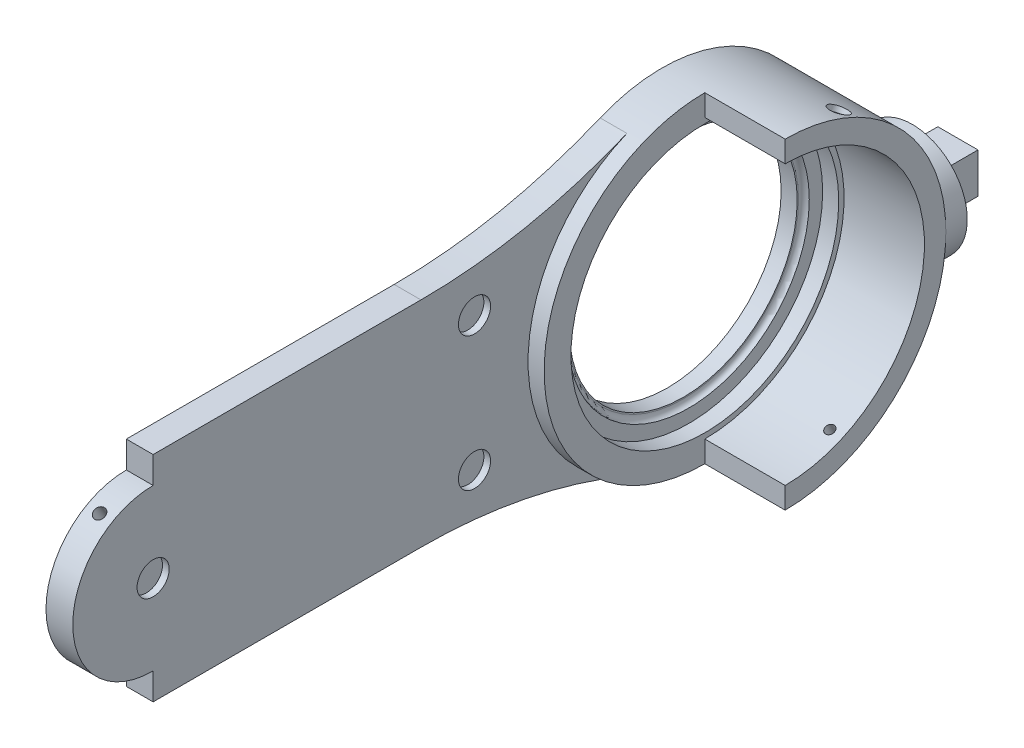
SolidWorks part; units mm, degrees
ref_plane "Front Plane" through (0, 0, 0) normal (0, 0, 1) x (1, 0, 0)
ref_plane "Top Plane" through (0, 0, 0) normal (0, 1, 0) x (1, 0, 0)
ref_plane "Right Plane" through (0, 0, 0) normal (1, 0, 0) x (0, 0, -1)
sketch "Sketch1" plane through (0, 0, 0) normal (1, 0, 0) x (0, 0, -1)
  line L0 (0, 0) -> (-200, 0) construction
  line L1 (-200, 40) -> (-200, -40) construction
  line L2 (-100, 40) -> (-100, -40) construction
  line L3 (-100, 40) -> (-200, 40)
  line L4 (-100, -40) -> (-200, -40)
  circle A0 centre (0, 0) radius 60
  circle A1 centre (0, 0) radius 45
  circle A2 centre (-200, 0) radius 40
  arc A3 (-100, 40) -> (-23.0769, 55.3846) centre (-100, 240) ccw
  arc A4 (-100, -40) -> (-23.0769, -55.3846) centre (-100, -240) cw
  circle A5 centre (-100, 0) radius 40 construction
  dimension "D1" = 120
  dimension "D2" = 90
  dimension "D4" = 80
  dimension "D3" = 200
extrude "Boss-Extrude3" add sketch "Sketch1" along normal blind 10 contours A0 A1 | A2 A0 | A2 region at (0, 0, 109.7273) region at (0, 0, 200) region at (0, 48.511, -32.3407)
sketch "Sketch4" plane through (10, 0, 0) normal (1, 0, 0) x (0, 0, -1)
  circle A0 centre (0, 0) radius 60
  circle A1 centre (0, 0) radius 50
  arc A2 (-23.0769, -55.3846) -> (-23.0769, 55.3846) centre (0, 0) ccw construction
  dimension "D1" = 100
extrude "Boss-Extrude4" add sketch "Sketch4" along normal blind 6
sketch "Sketch5" plane through (0, 0, 0) normal (-1, 0, 0) x (0, 0, 1)
  circle A0 centre (0, 0) radius 45 construction
  circle A1 centre (0, 0) radius 45
  circle A2 centre (0, 0) radius 42.5
  dimension "D1" = 85
extrude "Boss-Extrude5" add sketch "Sketch5" against normal offset from surface (8 mm away) 2 up to face at (10, 0, 120.2589)
fillet "Fillet1" radius 2 1 edges at (8, 0, -45)
sketch "Sketch6" plane through (0, 0, 0) normal (-1, 0, 0) x (0, 0, 1)
  circle A0 centre (0, 0) radius 42.5 construction
  circle A1 centre (0, 0) radius 42.5
  circle A2 centre (0, 0) radius 52.5
  dimension "D1" = 105
extrude "Cut-Extrude2" cut sketch "Sketch6" against normal blind 2
sketch "Sketch7" plane through (16, 0, 0) normal (1, 0, 0) x (0, 0, -1)
  line L0 (0, 60) -> (0, 50)
  line L1 (0, -50) -> (0, -60)
  circle A0 centre (0, 0) radius 60 construction
  circle A1 centre (0, 0) radius 50 construction
  circle A2 centre (0, 0) radius 50 construction
  arc A3 (0, -60) -> (0, 60) centre (0, 0) ccw
  arc A4 (0, -50) -> (0, 50) centre (0, 0) ccw
  arc A5 (0, -52) -> (0, 52) centre (0, 0) ccw
  circle M1 centre (0, 0) radius 60
  dimension "D1" = 2
extrude "Boss-Extrude6" add sketch "Sketch7" along normal blind 30 contours A5 L1 L0 M1 region at (16, 41.4777, -41.4777)
ref_plane "Plane2" through (0, 0, -60) normal (0, 0, -1) x (-1, 0, 0)
sketch "Sketch8" plane through (0, 0, -60) normal (0, 0, -1) x (-1, 0, 0)
  line L0 (-5, 0) -> (-46, 0) construction
  line L1 (-46, 60) -> (-46, -60) construction
  line L2 (-5, 0) -> (0, 0) construction
  circle A0 centre (-25.5, 0) radius 20.5
  point P10 (-46, 0)
  dimension "D1" = 41
  dimension "D2" = 5
extrude "Boss-Extrude7" add sketch "Sketch8" against normal up to surface up to face at (5, 0, 11.5385)
sketch "Sketch9" plane through (0, 0, -60) normal (0, 0, -1) x (-1, 0, 0)
  circle A0 centre (-25.5, 0) radius 15
  arc A1 (-5, 0) -> (-46, 0) centre (-25.5, 0) ccw construction
  arc A2 (-5, 0) -> (-46, 0) centre (-25.5, 0) ccw
  arc A4 (-46, 0) -> (-5, 0) centre (-25.5, 0) ccw
  dimension "D1" = 30
sketch "Sketch11" plane through (10, 0, 0) normal (1, 0, 0) x (0, 0, -1)
  line L0 (-200, 30) -> (-200, 40)
  line L1 (-200, -30) -> (-200, -40)
  arc A0 (-200, 40) -> (-200, -40) centre (-200, 0) ccw construction
  arc A1 (-200, 40) -> (-200, -40) centre (-200, 0) ccw
  arc A2 (-200, 30) -> (-200, -30) centre (-200, 0) ccw
  dimension "D1" = 10
extrude "Cut-Extrude4" cut sketch "Sketch11" against normal through all both and the other way through all
extrude "Boss-Extrude8" add sketch "Sketch9" along normal blind 8
sketch "Sketch12" plane through (0, 0, -60) normal (0, 0, -1) x (-1, 0, 0)
  line L1 (-33, -7.5) -> (-18, -7.5)
  line L2 (-33, -7.5) -> (-33, 7.5)
  line L3 (-33, 7.5) -> (-18, 7.5)
  line L4 (-18, -7.5) -> (-18, 7.5)
  line L5 (-33, -7.5) -> (-18, 7.5) construction
  line L6 (-33, 7.5) -> (-18, -7.5) construction
  point P0 (-25.5, 0)
  dimension "D1" = 15
extrude "Boss-Extrude9" add sketch "Sketch12" along normal blind 25
hole_wizard "CBORE for M3 Hexagon head bolts-Full thread-grades AB1" positions "3DSketch1" profile "Sketch13" counterbore size "M3" standard "GB" end condition up to next
sketch3d "3DSketch1"
  point P0 (41, -54.5436, -25)
  point P2 (41, 54.5436, -25)
  dimension "D1" = 5
  dimension "D2" = 25
  dimension "D3" = 5
  dimension "D4" = 25
sketch "Sketch13" plane through (41, -54.5436, -25) normal (1, 0, 0) x (0, 0.4167, -0.9091)
  line L0 (0, 0) -> (0, 8)
  line L1 (0, 8) -> (1.7, 8)
  line L3 (1.7, 8) -> (1.7, 2)
  line L4 (1.7, 2) -> (3.5, 2)
  line L5 (3.5, 2) -> (3.5, 0)
  line L7 (3.5, 0) -> (0, 0)
  line L11 (0, -6.35) -> (0, 107.95) construction
  dimension "Thru Hole Dia." = 3.4
  dimension "Thru Hole Depth" = 8
  dimension "C'Bore Dia." = 7
  dimension "C'Bore Depth" = 2
sketch3d "3DSketch2"
  circle A0 centre (5, 32.909, 219) radius 1.7 construction
  circle A1 centre (5, -32.909, 219) radius 1.7 construction
  circle A2 centre (5, 32.909, 219) radius 1.7
  circle A3 centre (5, -32.909, 219) radius 1.7
  point P0 (5.233, -19.8859, 222.4622)
  point P3 (5, 34.3812, 219.85)
  point P6 (5, -34.3812, 219.85)
  point P8 (5, 34.3812, 219.85)
  point P10 (5, -34.3812, 219.85)
ref_plane "Plane3" through (0, -119.5115, 69) normal (0, -0.866, 0.5) x (-1, 0, 0)
ref_plane "Plane4" through (0, 119.5115, 69) normal (0, 0.866, 0.5) x (1, 0, 0)
sketch "Sketch14" plane through (0, 119.5115, 69) normal (0, 0.866, 0.5) x (1, 0, 0)
  circle A0 centre (5, -173.2051) radius 2.05
  dimension "D1" = 4.1
extrude "Cut-Extrude5" cut sketch "Sketch14" against normal blind 15
sketch "Sketch15" plane through (0, -119.5115, 69) normal (0, -0.866, 0.5) x (-1, 0, 0)
  circle A0 centre (-5, -173.2051) radius 2.05
  dimension "D1" = 4.1
extrude "Cut-Extrude6" cut sketch "Sketch15" against normal blind 15
sketch "Sketch16" plane through (10, 0, 0) normal (1, 0, 0) x (0, 0, -1)
  circle A0 centre (-200, 0) radius 6
  dimension "D1" = 12
extrude "Cut-Extrude7" cut sketch "Sketch16" against normal blind 2.5
sketch "Sketch17" plane through (10, 0, 0) normal (1, 0, 0) x (0, 0, -1)
  line L0 (-75.2247, 0) -> (-111.3268, 0) construction
  circle A0 centre (-80, -25) radius 6
  circle A1 centre (-80, 25) radius 6
  arc A2 (-23.0769, 55.3846) -> (-23.0769, -55.3846) centre (0, 0) ccw construction
  dimension "D1" = 25
  dimension "D2" = 50
  dimension "D3" = 80
extrude "Cut-Extrude8" cut sketch "Sketch17" against normal blind 2.5
